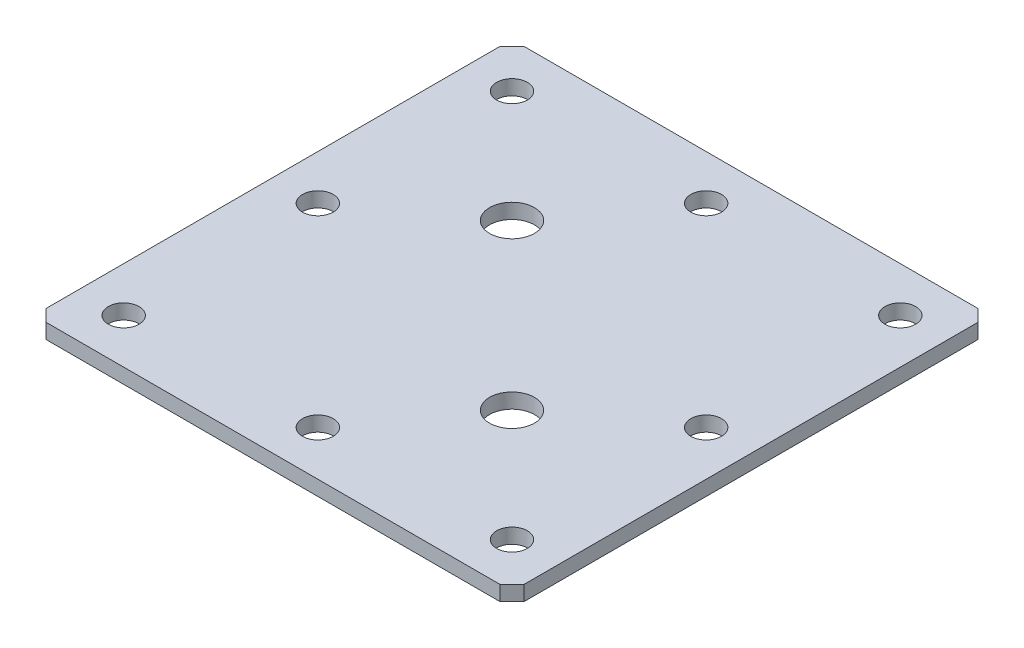
SolidWorks part; units mm, degrees
material "Rubber"
ref_plane "Front Plane" through (0, 0, 0) normal (0, 0, 1) x (1, 0, 0)
ref_plane "Top Plane" through (0, 0, 0) normal (0, 1, 0) x (1, 0, 0)
ref_plane "Right Plane" through (0, 0, 0) normal (1, 0, 0) x (0, 0, -1)
sketch "Sketch1" plane through (0, 0, 0) normal (0, 1, 0) x (1, 0, 0)
  line L0 (-57.4105, 21.9428) -> (-54.8705, 24.4828)
  line L1 (-54.8705, -77.1172) -> (41.6495, -77.1172)
  line L2 (-57.4105, -74.5772) -> (-57.4105, 21.9428)
  line L3 (-54.8705, 24.4828) -> (41.6495, 24.4828)
  line L4 (44.1895, -74.5772) -> (44.1895, 21.9428)
  line L5 (-57.4105, -77.1172) -> (44.1895, 24.4828) construction
  line L6 (-57.4105, 24.4828) -> (44.1895, -77.1172) construction
  line L7 (41.6495, 24.4828) -> (44.1895, 21.9428)
  line L8 (41.6495, -77.1172) -> (44.1895, -74.5772)
  line L9 (-57.4105, -74.5772) -> (-54.8705, -77.1172)
  line L10 (-47.8855, 14.9578) -> (-6.6105, 14.9578)
  line L11 (34.6645, -67.5922) -> (-47.8855, -67.5922) construction
  line L12 (34.6645, -67.5922) -> (34.6645, 14.9578) construction
  line L13 (34.6645, 14.9578) -> (-47.8855, 14.9578) construction
  line L14 (-47.8855, -67.5922) -> (-47.8855, 14.9578) construction
  line L15 (34.6645, -67.5922) -> (-47.8855, 14.9578) construction
  line L16 (34.6645, 14.9578) -> (-47.8855, -67.5922) construction
  line L17 (34.6645, -67.5922) -> (-6.6105, -67.5922)
  line L18 (-41.5355, -61.2422) -> (28.3145, -61.2422)
  line L19 (-41.5355, -61.2422) -> (-41.5355, 8.6078)
  line L20 (-41.5355, 8.6078) -> (28.3145, 8.6078)
  line L21 (28.3145, -61.2422) -> (28.3145, 8.6078)
  line L22 (-41.5355, -61.2422) -> (28.3145, 8.6078) construction
  line L23 (-41.5355, 8.6078) -> (28.3145, -61.2422) construction
  line L24 (-57.4105, -8.8547) -> (-24.073, -8.8547) construction
  line L25 (-24.073, -8.8547) -> (-24.073, 24.4828) construction
  line L26 (10.852, -77.1172) -> (10.852, -43.7797) construction
  line L27 (10.852, -43.7797) -> (44.1895, -43.7797) construction
  circle A0 centre (-47.8855, 14.9578) radius 3.2639
  circle A1 centre (-6.6105, 14.9578) radius 3.2639
  circle A2 centre (34.6645, 14.9578) radius 3.2639
  circle A3 centre (34.6645, -26.3172) radius 3.2639
  circle A4 centre (34.6645, -67.5922) radius 3.2639
  circle A5 centre (-6.6105, -67.5922) radius 3.2639
  circle A6 centre (-47.8855, -67.5922) radius 3.2639
  circle A7 centre (-47.8855, -26.3172) radius 3.2639
  circle A8 centre (-27.248, 14.9578) radius 4.7625 construction
  circle A9 centre (14.027, -67.5922) radius 4.7625 construction
  circle A10 centre (-24.073, -8.8547) radius 4.7625
  circle A11 centre (10.852, -43.7797) radius 4.7625
  point P0 (-6.6105, -26.3172)
  point P13 (-6.6105, -26.3172)
  point P34 (-6.6105, -26.3172)
  dimension "D13" = 6.5278
  dimension "D14" = 9.525
  dimension "D21" = 9.525
  dimension "D22" = 9.525
  dimension "D1" = 101.6
  dimension "D2" = 101.6
  dimension "D3" = 2.54
  dimension "D4" = 2.54
  dimension "D5" = 2.54
  dimension "D6" = 2.54
  dimension "D7" = 2.54
  dimension "D8" = 2.54
  dimension "D9" = 2.54
  dimension "D10" = 2.54
  dimension "D11" = 82.55
  dimension "D12" = 82.55
  dimension "D15" = 69.85
  dimension "D16" = 69.85
  dimension "D17" = 33.3375
  dimension "D18" = 33.3375
  dimension "D19" = 33.3375
  dimension "D20" = 33.3375
extrude "Boss-Extrude1" add sketch "Sketch1" along normal blind 3.175 contours L2 L9 L1 L8 L4 L7 L3 L0 A9 A4 A5 A8 A1 A0 A7 A6 A3 A2 L21 L18 L19 L20 | L18 L21 L20 L19 region at (-55.1245, 0, -22.1968) region at (-6.6105, 0, 26.3172)
